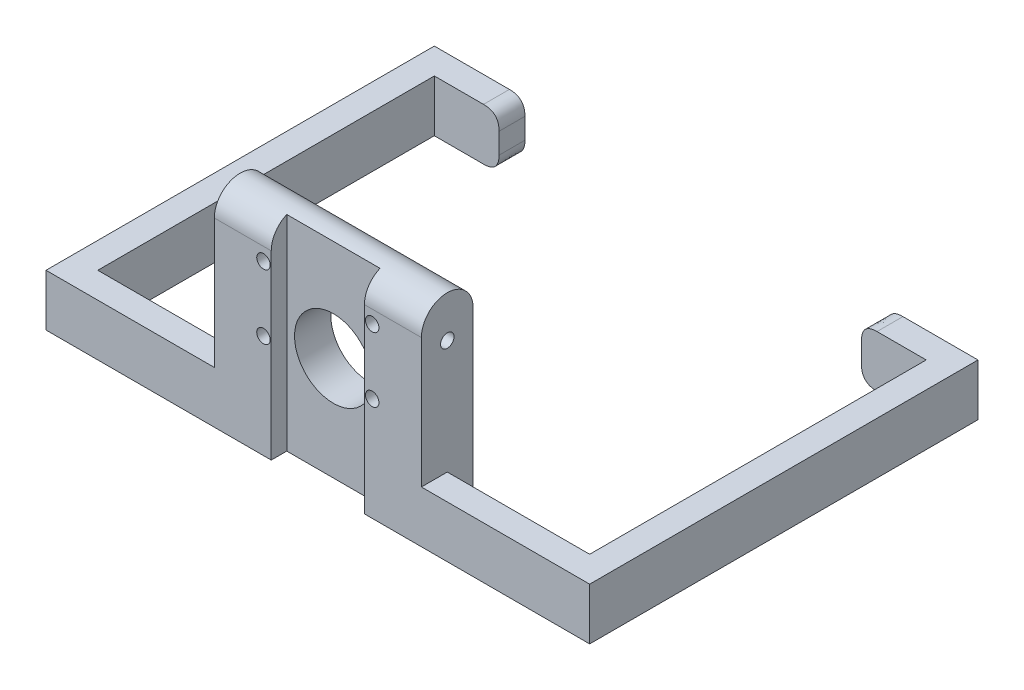
SolidWorks part; units mm, degrees
ref_plane "前基準面" through (0, 0, 0) normal (0, 0, 1) x (1, 0, 0)
ref_plane "上基準面" through (0, 0, 0) normal (0, 1, 0) x (1, 0, 0)
ref_plane "右基準面" through (0, 0, 0) normal (1, 0, 0) x (0, 0, -1)
sketch "草圖1" plane through (0, 0, 0) normal (0, 1, 0) x (1, 0, 0)
  line L1 (-52.5, -37.5) -> (52.5, -37.5)
  line L2 (-52.5, -37.5) -> (-52.5, 37.5)
  line L3 (-52.5, 37.5) -> (52.5, 37.5)
  line L4 (52.5, -37.5) -> (52.5, 37.5)
  line L5 (-52.5, -37.5) -> (52.5, 37.5) construction
  line L6 (-52.5, 37.5) -> (52.5, -37.5) construction
  line L7 (-47.5, -32.5) -> (47.5, -32.5)
  line L8 (-47.5, -32.5) -> (-47.5, 32.5)
  line L9 (-47.5, 32.5) -> (47.5, 32.5)
  line L10 (47.5, -32.5) -> (47.5, 32.5)
  line L11 (-47.5, -32.5) -> (47.5, 32.5) construction
  line L12 (-47.5, 32.5) -> (47.5, -32.5) construction
  point P0 (0, 0)
  point P6 (0, 0)
  dimension "D1" = 5
  dimension "D2" = 5
  dimension "D3" = 5
  dimension "D4" = 105
  dimension "D5" = 65
extrude "填料-伸長1" add sketch "草圖1" along normal blind 10
sketch "草圖2" plane through (0, 0, 37.5) normal (0, 0, 1) x (1, 0, 0)
  line L0 (-52.5, 0) -> (52.5, 0) construction
  line L1 (-20, 0) -> (20, 0)
  line L2 (-20, 0) -> (-20, 40)
  line L3 (-20, 40) -> (20, 40)
  line L4 (20, 0) -> (20, 40)
  line L5 (0, 40) -> (0, 0) construction
  dimension "D1" = 40
  dimension "D2" = 40
extrude "填料-伸長2" add sketch "草圖2" against normal blind 10
sketch "草圖3" plane through (0, 0, 37.5) normal (0, 0, 1) x (1, 0, 0)
  line L0 (0, 20) -> (0, 0) construction
  line L1 (-52.5, 0) -> (52.5, 0) construction
  circle A0 centre (0, 20) radius 7.5
  dimension "D1" = 15
  dimension "D2" = 20
extrude "除料-伸長1" cut sketch "草圖3" against normal up to next
sketch "草圖4" plane through (0, 0, -37.5) normal (0, 0, -1) x (-1, 0, 0)
  line L0 (-52.5, 0) -> (52.5, 0) construction
  line L1 (-35, 0) -> (35, 0)
  line L2 (-35, 0) -> (-35, 10)
  line L3 (-35, 10) -> (35, 10)
  line L4 (35, 0) -> (35, 10)
  line L5 (0, 10) -> (0, 0) construction
  line L6 (-52.5, 10) -> (52.5, 10) construction
  dimension "D1" = 70
extrude "除料-伸長2" cut sketch "草圖4" against normal up to next
hole_wizard "Ø1.0 (1) 直徑孔1" positions "草圖5" profile "草圖7" hole size "Ø1.0" standard "ISO"
sketch "草圖5" plane through (20, 0, 0) normal (1, 0, 0) x (0, 0, -1)
  line L0 (-32.5, 40) -> (-32.5, 32) construction
  line L1 (-27.5, 40) -> (-37.5, 40) construction
  point P0 (-32.5, 32)
  dimension "D1" = 8
sketch "草圖7" plane through (20, 32, 32.5) normal (0, 1, 0) x (0, 0, -1)
  line L0 (0, 0) -> (0, 7.8811)
  line L1 (0, 7.8811) -> (1.3, 7.1)
  line L2 (1.3, 7.1) -> (1.3, 0)
  line L5 (1.3, 0) -> (0, 0)
  line L10 (0, 7.8811) -> (-1.3, 7.1) construction
  line L11 (0, -6.35) -> (0, 107.95) construction
  dimension "鑽孔直徑" = 2.6
  dimension "鑽孔深度" = 7.1
  dimension "導頭角度" = 118
mirror "鏡射1" about plane through (0, 0, 0) normal (1, 0, 0) of "Ø1.0 (1) 直徑孔1"
fillet "圓角2" 2 edges at (0, 40, 27.5) (0, 40, 37.5) type full round first side face at (-7.5, 20, 27.5) second side face at (7.5, 20, 37.5) middle face at (0, 40, 32.5)
fillet "圓角3" radius 3 4 edges at (35, 0, -35) (35, 10, -35) (-35, 0, -35) (-35, 10, -35) conic rho 0.5
sketch "草圖8" plane through (0, 0, 37.5) normal (0, 0, 1) x (1, 0, 0)
  line L0 (0, 26.25) -> (0, 20) construction
  line L1 (-10.5, 32.5) -> (10.5, 32.5) construction
  line L2 (-10.5, 32.5) -> (-10.5, 20) construction
  line L3 (-10.5, 20) -> (10.5, 20) construction
  line L4 (10.5, 32.5) -> (10.5, 20) construction
  line L5 (-10.5, 32.5) -> (10.5, 20) construction
  line L6 (-10.5, 20) -> (10.5, 32.5) construction
  circle A0 centre (-10.5, 32.5) radius 1.3
  circle A1 centre (-10.5, 20) radius 1.3
  circle A2 centre (10.5, 32.5) radius 1.3
  circle A3 centre (10.5, 20) radius 1.3
  point P0 (0, 26.25)
  dimension "D3" = 2.6
  dimension "D1" = 21
  dimension "D2" = 12.5
extrude "除料-伸長3" cut sketch "草圖8" against normal through all
sketch "草圖9" plane through (0, 0, 37.5) normal (0, 0, 1) x (1, 0, 0)
  line L1 (-9, -5) -> (9, -5)
  line L2 (-9, -5) -> (-9, 45)
  line L3 (-9, 45) -> (9, 45)
  line L4 (9, -5) -> (9, 45)
  line L5 (-9, -5) -> (9, 45) construction
  line L6 (-9, 45) -> (9, -5) construction
  point P0 (0, 20)
  dimension "D1" = 50
  dimension "D2" = 18
extrude "除料-伸長4" cut sketch "草圖9" against normal blind 3
